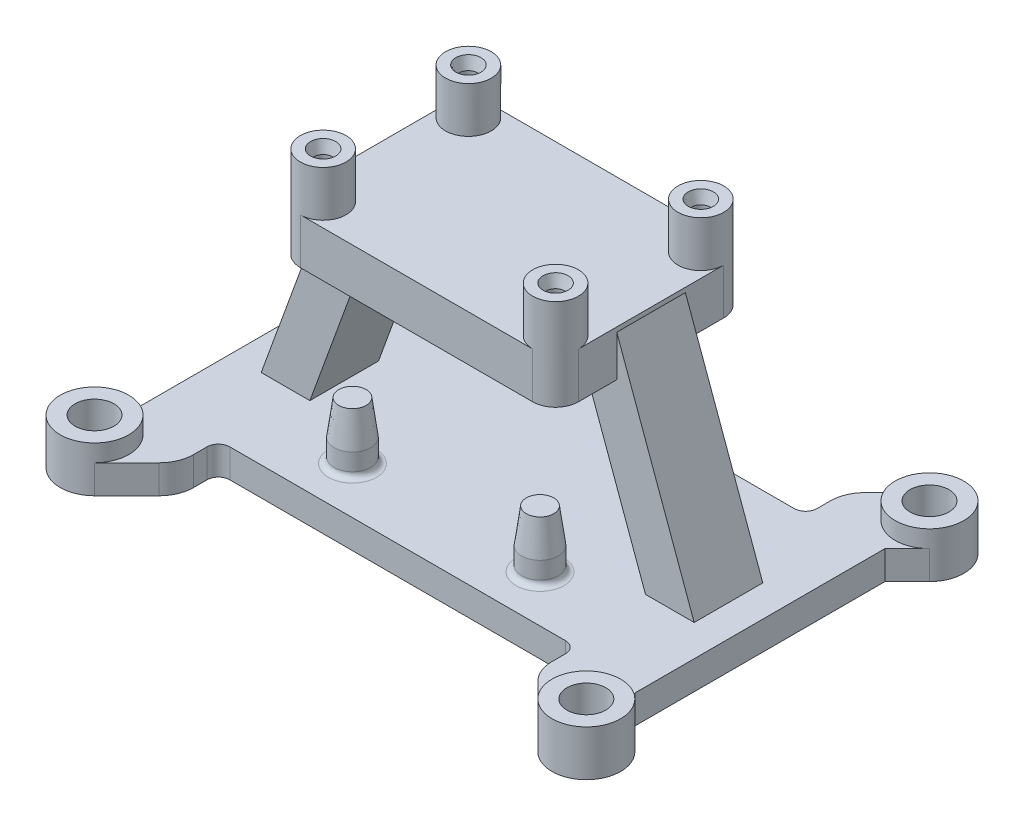
SolidWorks part; units mm, degrees
ref_plane "Front Plane" through (0, 0, 0) normal (0, 0, 1) x (1, 0, 0)
ref_plane "Top Plane" through (0, 0, 0) normal (0, 1, 0) x (1, 0, 0)
ref_plane "Right Plane" through (0, 0, 0) normal (1, 0, 0) x (0, 0, -1)
sketch "Sketch1" plane through (0, 0, 0) normal (0, 1, 0) x (1, 0, 0)
  line L1 (-21.5, 15) -> (21.5, 15) construction
  line L2 (-21.5, 15) -> (-21.5, -15) construction
  line L3 (-21.5, -15) -> (21.5, -15) construction
  line L4 (21.5, 15) -> (21.5, -15) construction
  line L5 (-21.5, 15) -> (21.5, -15) construction
  line L6 (-21.5, -15) -> (21.5, 15) construction
  circle A0 centre (-21.5, 15) radius 1.7
  circle A1 centre (21.5, 15) radius 1.7
  circle A2 centre (21.5, -15) radius 1.7
  circle A3 centre (-21.5, -15) radius 1.7
  circle A4 centre (-21.5, 15) radius 3
  circle A5 centre (-21.5, -15) radius 3
  circle A6 centre (21.5, -15) radius 3
  circle A7 centre (21.5, 15) radius 3
  point P0 (0, 0)
  dimension "D3" = 3.4
  dimension "D4" = 6
  dimension "D1" = 43
  dimension "D2" = 30
extrude "Boss-Extrude1" add sketch "Sketch1" along normal blind 4
sketch "Sketch2" plane through (0, 0, 0) normal (0, 1, 0) x (1, 0, 0)
  line L0 (-21.5, 15) -> (-18.6716, 12.1716) construction
  line L1 (-19.3787, 17.1213) -> (-16.5503, 14.2929)
  line L2 (-23.6213, 12.8787) -> (-21.6716, 10.9289)
  line L3 (-21.5, -15) -> (-18.6716, -12.1716) construction
  line L4 (-23.6213, -12.8787) -> (-21.6716, -10.9289)
  line L5 (-19.3787, -17.1213) -> (-16.5503, -14.2929)
  line L6 (-18.6716, 12.1716) -> (-18.6716, -12.1716) construction
  line L7 (-15.6716, 12.1716) -> (-15.6716, -12.1716)
  line L8 (-21.6716, 10.9289) -> (-21.6716, -10.9289)
  line L9 (0, -1000) -> (0, 49000) construction
  line L10 (18.6716, 12.1716) -> (18.6716, -12.1716) construction
  line L11 (21.5, -15) -> (18.6716, -12.1716) construction
  line L12 (21.5, 15) -> (18.6716, 12.1716) construction
  line L13 (21.6716, 10.9289) -> (21.6716, -10.9289)
  line L14 (15.6716, 12.1716) -> (15.6716, -12.1716)
  line L15 (19.3787, -17.1213) -> (16.5503, -14.2929)
  line L16 (23.6213, -12.8787) -> (21.6716, -10.9289)
  line L17 (23.6213, 12.8787) -> (21.6716, 10.9289)
  line L18 (19.3787, 17.1213) -> (16.5503, 14.2929)
  arc A0 (-19.3787, 17.1213) -> (-23.6213, 12.8787) centre (-21.5, 15) ccw
  circle A2 centre (-21.5, 15) radius 3 construction
  arc A3 (-23.6213, -12.8787) -> (-19.3787, -17.1213) centre (-21.5, -15) ccw
  arc A4 (-16.5503, -14.2929) -> (-15.6716, -12.1716) centre (-18.6716, -12.1716) ccw
  circle A5 centre (-21.5, -15) radius 3 construction
  arc A6 (-15.6716, 12.1716) -> (-16.5503, 14.2929) centre (-18.6716, 12.1716) ccw
  arc A7 (-16.5503, -14.2929) -> (-15.6716, -12.1716) centre (-18.6716, -12.1716) ccw
  arc A8 (-15.6716, 12.1716) -> (-16.5503, 14.2929) centre (-18.6716, 12.1716) ccw
  arc A9 (15.6716, 12.1716) -> (16.5503, 14.2929) centre (18.6716, 12.1716) cw
  arc A10 (16.5503, -14.2929) -> (15.6716, -12.1716) centre (18.6716, -12.1716) cw
  arc A11 (15.6716, 12.1716) -> (16.5503, 14.2929) centre (18.6716, 12.1716) cw
  arc A12 (16.5503, -14.2929) -> (15.6716, -12.1716) centre (18.6716, -12.1716) cw
  arc A13 (23.6213, -12.8787) -> (19.3787, -17.1213) centre (21.5, -15) cw
  arc A14 (19.3787, 17.1213) -> (23.6213, 12.8787) centre (21.5, 15) cw
  point P2 (-20.0858, 13.5858)
  point P13 (-20.0858, -13.5858)
  point P20 (-18.6716, 0)
  point P41 (18.6716, 0)
  point P42 (20.0858, -13.5858)
  point P43 (20.0858, 13.5858)
  dimension "D1" = 45
  dimension "D2" = 45
  dimension "D3" = 4
  dimension "D4" = 4
  dimension "D5" = 3
  dimension "D6" = 3
extrude "Boss-Extrude2" add sketch "Sketch2" along normal blind 2.5 contours L7 A6 L1 A0 L2 L8 L4 A3 L5 A4 | A14 L18 A9 L14 A10 L15 A13 L16 L13 L17 region at (-19.3328, 0, 0) region at (19.3328, 0, 0)
extrude "Cut-Extrude1" cut sketch "Sketch1<2>" against normal through all both and the other way through all contours A3 | A0 | A1 | A2 region at (-21.5, 0, -15) region at (21.5, 0, -15) region at (21.5, 0, 15) region at (-21.5, 0, 15)
sketch "Sketch1<2>" plane through (0, 0, 0) normal (0, 1, 0) x (1, 0, 0) same geometry as "Sketch1"
sketch "Sketch4" plane through (0, 0, 0) normal (0, 1, 0) x (1, 0, 0)
  line L0 (15.6716, 12.1716) -> (15.6716, -12.1716) construction
  line L1 (-15.6716, 10) -> (15.6716, 10)
  line L2 (-15.6716, 10) -> (-15.6716, -10)
  line L3 (-15.6716, -10) -> (15.6716, -10)
  line L4 (15.6716, 10) -> (15.6716, -10)
  line L5 (-15.6716, 10) -> (15.6716, -10) construction
  line L6 (-15.6716, -10) -> (15.6716, 10) construction
  point P0 (0, 0)
  dimension "D1" = 20
extrude "Boss-Extrude3" add sketch "Sketch4" along normal up to surface (2.5 mm away) up to face at (-18.9122, 2.5, 0)
sketch "Sketch5" plane through (0, 2.5, 0) normal (0, 1, 0) x (1, 0, 0)
  line L0 (-1005.1394, -7.5) -> (48994.8606, -7.5) construction
  line L1 (-10.15, 8) -> (10.15, 8) construction
  line L2 (-10.15, 8) -> (-10.15, -8) construction
  line L3 (-10.15, -8) -> (10.15, -8) construction
  line L4 (10.15, 8) -> (10.15, -8) construction
  line L5 (-10.15, 8) -> (10.15, -8) construction
  line L6 (-10.15, -8) -> (10.15, 8) construction
  line L7 (-9.65, -1006.7474) -> (-9.65, 48993.2526) construction
  circle A0 centre (-8.05, -5.9) radius 1.6
  circle A1 centre (8.35, -5.9) radius 1.6
  point P0 (0, 0)
  dimension "D3" = 3.2
  dimension "D6" = 1.8
  dimension "D1" = 16
  dimension "D2" = 20.3
  dimension "D4" = 0.5
  dimension "D5" = 0.5
extrude "Boss-Extrude4" add sketch "Sketch5" along normal blind 5
chamfer "Chamfer1" distance 3 distance2 0.4 2 edges at (8.35, 7.5, 7.5) (-8.05, 7.5, 7.5) first distance on face at (8.35, 7.5, 7.5) first distance on face at (-8.05, 7.5, 7.5)
fillet "Fillet1" radius 0.5 2 edges at (8.35, 2.5, 7.5) (-8.05, 2.5, 7.5)
fillet "Fillet2" radius 1 4 edges at (-15.6716, 1.25, -10) (15.6716, 1.25, -10) (15.6716, 1.25, 10) (-15.6716, 1.25, 10)
sketch "Sketch6" plane through (0, 0, 0) normal (0, 0, 1) x (1, 0, 0)
  line L0 (-14.6716, 2.5) -> (-9.212, 17.5)
  line L1 (-9.212, 17.5) -> (9.212, 17.5)
  line L2 (-201005.1394, 2.5) -> (248994.8606, 2.5) construction
  line L3 (-14.6716, 2.5) -> (-18.9283, 2.5)
  line L4 (-18.9283, 2.5) -> (-12.0128, 21.5)
  line L5 (-12.0128, 21.5) -> (12.0128, 21.5)
  line L6 (-10.15, 2.5) -> (10.15, 2.5) construction
  line L7 (0, -1000) -> (0, 49000) construction
  line L8 (18.9283, 2.5) -> (12.0128, 21.5)
  line L9 (14.6716, 2.5) -> (18.9283, 2.5)
  line L10 (14.6716, 2.5) -> (9.212, 17.5)
  point P11 (-18.5, 2.5)
  point P17 (-20.2738, -1.1966)
  point P18 (0, 21.5)
  point P21 (0, 17.5)
  dimension "D1" = 70
  dimension "D2" = 4
  dimension "D3" = 4
  dimension "D4" = 15
extrude "Boss-Extrude5" add sketch "Sketch6" along normal blind 3 and the other way blind 3
sketch "Sketch7" plane through (0, 21.5, 0) normal (0, 1, 0) x (1, 0, 0)
  line L1 (-12.7, 8.89) -> (12.7, 8.89) construction
  line L2 (-12.7, 8.89) -> (-12.7, -8.89) construction
  line L3 (-12.7, -8.89) -> (12.7, -8.89) construction
  line L4 (12.7, 8.89) -> (12.7, -8.89) construction
  line L5 (-12.7, 8.89) -> (12.7, -8.89) construction
  line L6 (-12.7, -8.89) -> (12.7, 8.89) construction
  line L7 (-10.16, 6.35) -> (10.16, 6.35) construction
  line L8 (-10.16, 6.35) -> (-10.16, -6.35) construction
  line L9 (-10.16, -6.35) -> (10.16, -6.35) construction
  line L10 (10.16, 6.35) -> (10.16, -6.35) construction
  line L11 (-10.16, 6.35) -> (10.16, -6.35) construction
  line L12 (-10.16, -6.35) -> (10.16, 6.35) construction
  circle A0 centre (-10.16, 6.35) radius 0.8
  circle A1 centre (10.16, 6.35) radius 0.8
  circle A2 centre (10.16, -6.35) radius 0.8
  circle A3 centre (-10.16, -6.35) radius 0.8
  circle A4 centre (-10.16, 6.35) radius 2
  circle A5 centre (-10.16, -6.35) radius 2
  circle A6 centre (10.16, 6.35) radius 2
  circle A7 centre (10.16, -6.35) radius 2
  point P0 (0, 0)
  point P6 (0, 0)
  dimension "D5" = 1.6
  dimension "D6" = 4
  dimension "D1" = 17.78
  dimension "D2" = 25.4
  dimension "D3" = 12.7
  dimension "D4" = 20.32
extrude "Boss-Extrude6" add sketch "Sketch7" along normal blind 4 separate body
sketch "Sketch8" plane through (0, 21.5, 0) normal (0, 1, 0) x (1, 0, 0)
  line L1 (10.16, -8.35) -> (-10.16, -8.35)
  line L2 (12.16, -6.35) -> (12.16, 6.35)
  line L3 (10.16, 8.35) -> (-10.16, 8.35)
  line L4 (-12.16, -6.35) -> (-12.16, 6.35)
  line L5 (11.4604, -7.8696) -> (-11.4604, 7.8696) construction
  line L6 (11.4604, 7.8696) -> (-11.4604, -7.8696) construction
  circle A0 centre (-10.16, 6.35) radius 2 construction
  circle A1 centre (-10.16, -6.35) radius 2 construction
  circle A2 centre (10.16, -6.35) radius 2 construction
  circle A3 centre (10.16, 6.35) radius 2 construction
  arc A4 (-12.16, -6.35) -> (-10.16, -8.35) centre (-10.16, -6.35) ccw
  arc A5 (10.16, -8.35) -> (12.16, -6.35) centre (10.16, -6.35) ccw
  arc A6 (12.16, 6.35) -> (10.16, 8.35) centre (10.16, 6.35) ccw
  arc A7 (-10.16, 8.35) -> (-12.16, 6.35) centre (-10.16, 6.35) ccw
  point P0 (0, 0)
  point P5 (0, 0)
extrude "Boss-Extrude7" add sketch "Sketch8" against normal blind 4
extrude "Cut-Extrude2" cut sketch "Sketch7<2>" against normal blind 4 contours A3 | A0 | A1 | A2 region at (-10.16, 21.5, -6.35) region at (10.16, 21.5, -6.35) region at (-10.16, 21.5, 6.35)
sketch "Sketch7<2>" plane through (0, 21.5, 0) normal (0, 1, 0) x (1, 0, 0) same geometry as "Sketch7"
chamfer "Chamfer2" distance 0.3 distance2 1 4 edges at (-10.16, 25.5, 7.15) (10.16, 25.5, 7.15) (10.16, 25.5, -5.55) (-10.16, 25.5, -5.55) first distance on face at (-10.16, 25.5, 8.35) first distance on face at (10.16, 25.5, 8.35) first distance on face at (10.16, 25.5, -4.35) first distance on face at (-10.16, 25.5, -4.35)
